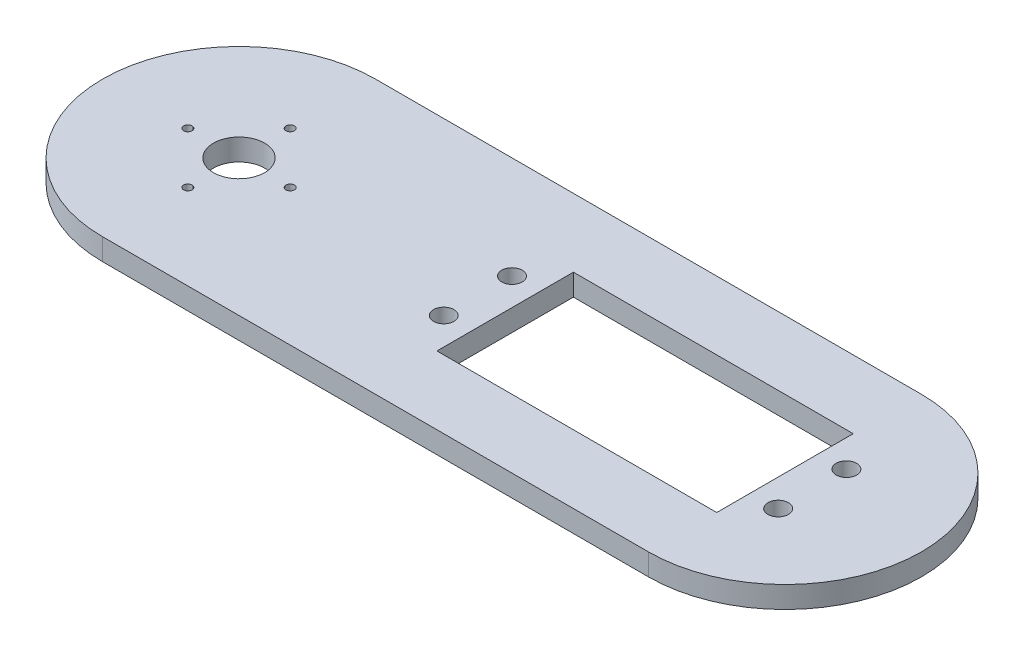
SolidWorks part; units mm, degrees
material "Pine"
ref_plane "Front Plane" through (0, 0, 0) normal (0, 0, 1) x (1, 0, 0)
ref_plane "Top Plane" through (0, 0, 0) normal (0, 1, 0) x (1, 0, 0)
ref_plane "Right Plane" through (0, 0, 0) normal (1, 0, 0) x (0, 0, -1)
sketch "Sketch3" plane through (0, 0, 0) normal (0, 1, 0) x (1, 0, 0)
  line L0 (-40.3723, 0) -> (39.6277, 0) construction
  line L1 (-40.3723, 20) -> (39.6277, 20)
  line L2 (-40.3723, -20) -> (39.6277, -20)
  line L4 (39.6277, 10) -> (-1.3723, 10)
  line L5 (39.6277, 10) -> (39.6277, -10)
  line L6 (39.6277, -10) -> (-1.3723, -10)
  line L7 (-1.3723, 10) -> (-1.3723, -10)
  arc A0 (-40.3723, 20) -> (-40.3723, -20) centre (-40.3723, 0) ccw
  arc A1 (39.6277, -20) -> (39.6277, 20) centre (39.6277, 0) ccw
  circle A2 centre (-40.3723, 0) radius 3.75
  circle A3 centre (-32.8723, 0) radius 0.625
  circle A4 centre (-5.3723, 5) radius 1.5
  circle A5 centre (-5.3723, -5) radius 1.5
  circle A6 centre (43.6277, 5) radius 1.5
  circle A7 centre (43.6277, -5) radius 1.5
  circle A8 centre (-47.8723, 0) radius 0.625
  circle A9 centre (-40.3723, 7.5) radius 0.625
  circle A10 centre (-40.3723, -7.5) radius 0.625
  point P3 (-0.3723, 0)
  dimension "D1" = 20
  dimension "D7" = 7.5
  dimension "D9" = 1.25
  dimension "D26" = 3
  dimension "D27" = 3
  dimension "D28" = 3
  dimension "D29" = 3
  dimension "D2" = 80
  dimension "D3" = 0
  dimension "D4" = 20
  dimension "D5" = 10
  dimension "D6" = 41
  dimension "D8" = 20
  dimension "D10" = 7.5
  dimension "D12" = 7.5
  dimension "D13" = 7.5
  dimension "D16" = 7.5
  dimension "D18" = 5
  dimension "D19" = 5
  dimension "D20" = 5
  dimension "D21" = 5
  dimension "D22" = 4
  dimension "D23" = 4
  dimension "D24" = 4
  dimension "D25" = 4
extrude "Boss-Extrude1" add sketch "Sketch3" along normal blind 3.175
